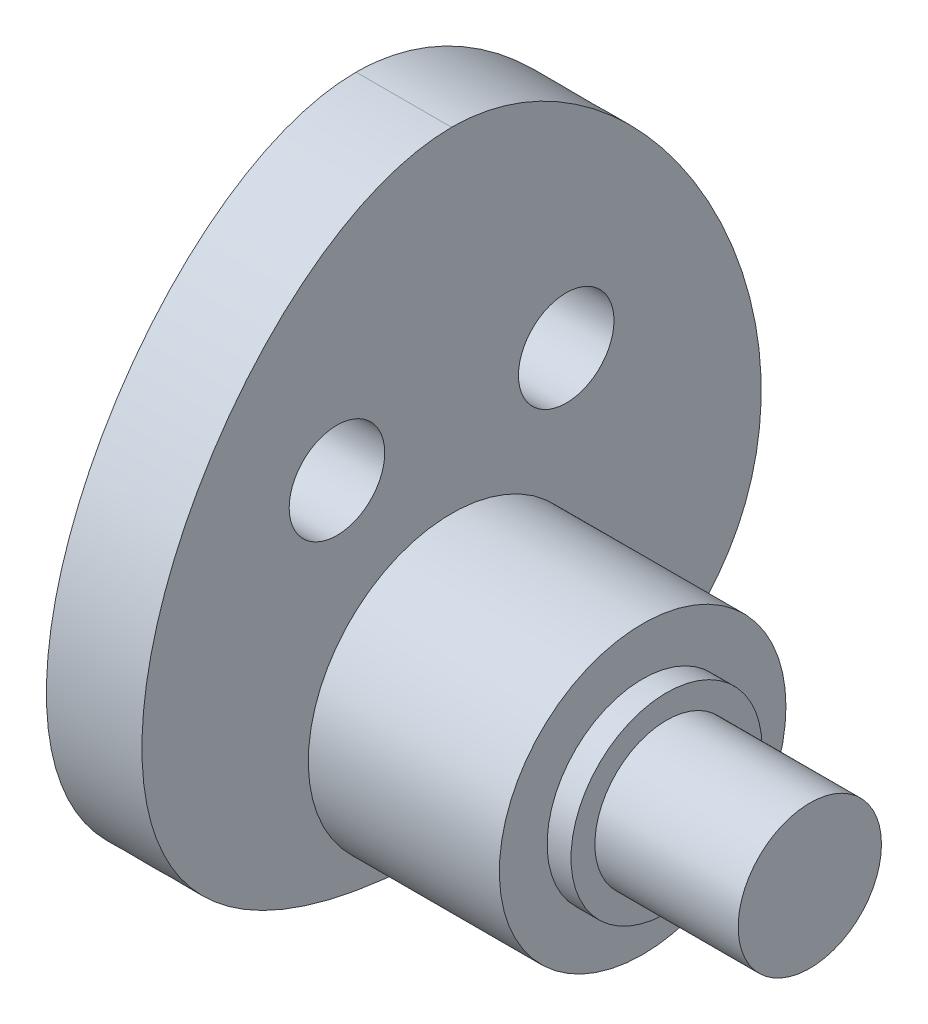
SolidWorks part; units mm, degrees
ref_plane "Front Plane" through (0, 0, 0) normal (0, 0, 1) x (1, 0, 0)
ref_plane "Top Plane" through (0, 0, 0) normal (0, 1, 0) x (1, 0, 0)
ref_plane "Right Plane" through (0, 0, 0) normal (1, 0, 0) x (0, 0, -1)
sketch "Sketch1" plane through (0, 0, 0) normal (1, 0, 0) x (0, 0, -1)
  line L0 (0, 0) -> (0, -3) construction
  line L1 (0, 0) -> (-2, -3.4641) construction
  line L2 (0, 0) -> (-4.3301, -2.5) construction
  line L3 (0, 0) -> (-6, 0) construction
  line L4 (0, 0) -> (-6.0622, 3.5) construction
  line L5 (0, 0) -> (-4, 6.9282) construction
  line L6 (0, 0) -> (0, 10) construction
  circle A4 centre (0, 0) radius 2.5
  spline S0 degree 3 poles (0, 10) (-5.5754, 10) (-11.2568, -3) (0, -3) knots 0 0 0 0 1 1 1 1
  spline S1 degree 3 poles (0, 10) (5.5754, 10) (11.2568, -3) (0, -3) knots 0 0 0 0 1 1 1 1
  dimension "D2" = 10
  dimension "D4" = 5
  dimension "D5" = 3
  dimension "D6" = 4
  dimension "D7" = 5
  dimension "D8" = 6
  dimension "D9" = 7
  dimension "D10" = 8
  dimension "D11" = 30
  dimension "D12" = 30
  dimension "D13" = 30
  dimension "D14" = 30
  dimension "D15" = 30
extrude "Boss-Extrude1" add sketch "Sketch1" along normal blind 2
sketch "Sketch2" plane through (2, 0, 0) normal (1, 0, 0) x (0, 0, -1)
  circle A0 centre (0, 0) radius 3
  dimension "D2" = 6
extrude "Boss-Extrude2" add sketch "Sketch2" along normal blind 7.5
sketch "Sketch3" plane through (0, 0, 0) normal (-1, 0, 0) x (0, 0, 1)
  circle A1 centre (-2.4, 4.8) radius 1
  circle A2 centre (2.4, 4.8) radius 1
  dimension "D2" = 2
  dimension "D3" = 4.8
  dimension "D5" = 2.4
  dimension "D6" = 2.4
extrude "Cut-Extrude1" cut sketch "Sketch3" against normal up to next
chamfer "Chamfer1" distance 1 angle 45 1 edges at (2, 0, -2.5)
sketch "Sketch4" plane through (9.5, 0, 0) normal (1, 0, 0) x (0, 0, -1)
  circle A0 centre (0, 0) radius 1.5
  dimension "D1" = 3
extrude "Cut-Extrude2" cut sketch "Sketch4" against normal blind 3 flip side to cut
sketch "Sketch5" plane through (6.5, 0, 0) normal (1, 0, 0) x (0, 0, -1)
  circle A0 centre (0, 0) radius 2
  dimension "D1" = 4
extrude "Cut-Extrude3" cut sketch "Sketch5" against normal blind 0.5 flip side to cut
